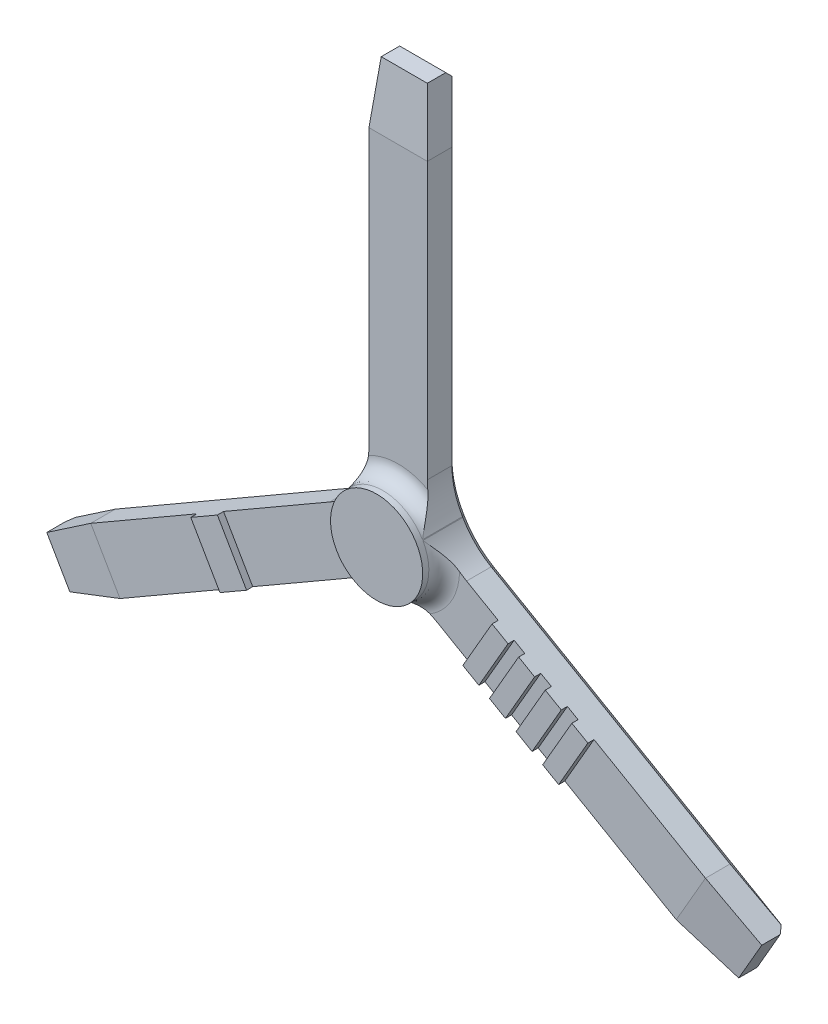
SolidWorks part; units mm, degrees
ref_plane "Front Plane" through (0, 0, 0) normal (0, 0, 1) x (1, 0, 0)
ref_plane "Top Plane" through (0, 0, 0) normal (0, 1, 0) x (1, 0, 0)
ref_plane "Right Plane" through (0, 0, 0) normal (1, 0, 0) x (0, 0, -1)
sketch "Sketch1" plane through (0, 0, 0) normal (0, 0, 1) x (1, 0, 0)
  line L0 (-1.9, 24) -> (1.9, 24) construction
  line L1 (0, 0) -> (0, 24) construction
  line L2 (-1.9, 24) -> (-1.9, 26)
  line L3 (-1.9, 26) -> (1.9, 26)
  line L4 (1.9, 26) -> (1.9, 24)
  line L5 (23.4667, -11.3546) -> (21.5667, -14.6454)
  line L6 (21.5667, -14.6454) -> (19.8346, -13.6454)
  line L7 (21.7346, -10.3546) -> (23.4667, -11.3546)
  line L8 (-21.5667, -14.6454) -> (-23.4667, -11.3546)
  line L9 (-23.4667, -11.3546) -> (-21.7346, -10.3546)
  line L10 (-19.8346, -13.6454) -> (-21.5667, -14.6454)
  line L11 (0, 0) -> (1.9, 24) construction
  line L12 (0, 0) -> (19.8346, -13.6454) construction
  line L13 (-1.9, 24) -> (-1.9, 1.097)
  line L14 (-1.9, 1.097) -> (-21.7346, -10.3546)
  line L15 (-19.8346, -13.6454) -> (0, -2.1939)
  line L16 (0, -2.1939) -> (19.8346, -13.6454)
  line L17 (21.7346, -10.3546) -> (1.9, 1.097)
  line L18 (1.9, 1.097) -> (1.9, 24)
  circle A0 centre (0, 0) radius 24 construction
  dimension "D1" = 48
  dimension "D2" = 3.8
  dimension "D3" = 2
  dimension "D4" = 120
  dimension "D5" = 24.0751
  dimension "D6" = 3
extrude "Boss-Extrude1" add sketch "Sketch1" along normal blind 2 contours L18 A0 L13 L14 L15 L16 L17 region at (0, 0, 0)
chamfer "Chamfer1" distance 4 distance2 0.4 3 edges at (22.5167, -13, 2) (-22.5167, -13, 2) (0, 26, 2) first distance on face at (0, 0, 2)
chamfer "Chamfer2" distance 0.4 distance2 4 3 edges at (23.4667, -11.3546, 0.8) (-1.9, 26, 0.8) (-21.5667, -14.6454, 0.8) first distance on face at (22.5167, -13, 0.8) first distance on face at (0, 26, 0.8) first distance on face at (-22.5167, -13, 0.8)
chamfer "Chamfer3" distance 4 distance2 0.4 3 edges at (1.9, 26, 0.8) (21.5667, -14.6454, 0.8) (-23.4667, -11.3546, 0.8) first distance on face at (1.9, 15.2388, 1.12) first distance on face at (12.2472, -9.2648, 1.12) first distance on face at (-14.1472, -5.9739, 1.12)
sketch "Sketch2" plane through (0, 0, 0) normal (0, 0, -1) x (-1, 0, 0)
  circle A0 centre (0, 0) radius 3
  dimension "D1" = 6
extrude "Boss-Extrude2" add sketch "Sketch2" against normal blind 3.4
fillet "Fillet1" radius 5 6 edges at (1.9, 2.3216, 1) (2.9606, 0.4846, 1) (1.0606, -2.8063, 1) (-1.0606, -2.8063, 1) (-2.9606, 0.4846, 1) (-1.9, 2.3216, 1)
fillet "Fillet2" radius 1 3 edges at (0, 3, 2) (2.5981, -1.5, 2) (-2.5981, -1.5, 2)
chamfer "Chamfer4" distance 0.4 angle 45 18 edges at (22.5167, -13, 0) (-22.5167, -13, 0) (0, 26, 0) (12.2293, -4.8667, 0) (3.4082, 0.4282, 0) (2.5981, 1.5, 0) (2.0749, 2.7374, 0) (1.9, 13.0242, 0) (-12.2293, -4.8667, 0) (-3.4082, 0.4282, 0) (-2.5981, 1.5, 0) (-2.0749, 2.7374, 0) (-1.9, 13.0242, 0) (10.3293, -8.1576, 0) (1.3332, -3.1657, 0) (0, -3, 0) (-1.3332, -3.1657, 0) (-10.3293, -8.1576, 0)
sketch "Sketch3" plane through (0, 0, 2) normal (0, 0, 1) x (1, 0, 0)
  line L0 (-12.2293, -4.8667) -> (-10.3293, -8.1576) construction
  line L1 (-4.4561, -0.3788) -> (-20.0026, -9.3546) construction
  line L2 (-2.5561, -3.6697) -> (-18.1026, -12.6454) construction
  line L3 (-13.0953, -5.3667) -> (-11.1953, -8.6576)
  line L4 (2.5561, -3.6697) -> (18.1026, -12.6454) construction
  line L5 (10.3293, -8.1576) -> (12.2293, -4.8667) construction
  line L6 (20.0026, -9.3546) -> (4.4561, -0.3788) construction
  line L7 (-13.0953, -5.3667) -> (-11.3633, -4.3667)
  line L8 (-11.1953, -8.6576) -> (-9.4633, -7.6576)
  line L9 (-11.3633, -4.3667) -> (-9.4633, -7.6576)
  line L10 (-13.0953, -5.3667) -> (-9.4633, -7.6576) construction
  line L11 (-11.1953, -8.6576) -> (-11.3633, -4.3667) construction
  line L12 (11.7097, -4.5667) -> (9.8097, -7.8576)
  line L13 (11.7097, -4.5667) -> (12.7489, -5.1667)
  line L14 (9.8097, -7.8576) -> (10.8489, -8.4576)
  line L15 (12.7489, -5.1667) -> (10.8489, -8.4576)
  line L16 (11.7097, -4.5667) -> (10.8489, -8.4576) construction
  line L17 (9.8097, -7.8576) -> (12.7489, -5.1667) construction
  line L18 (8.0776, -6.8576) -> (9.1169, -7.4576)
  line L19 (11.0169, -4.1667) -> (9.1169, -7.4576)
  line L20 (9.9776, -3.5667) -> (8.0776, -6.8576)
  line L21 (9.9776, -3.5667) -> (11.0169, -4.1667)
  line L22 (6.3456, -5.8576) -> (7.3848, -6.4576)
  line L23 (9.2848, -3.1667) -> (7.3848, -6.4576)
  line L24 (8.2456, -2.5667) -> (6.3456, -5.8576)
  line L25 (8.2456, -2.5667) -> (9.2848, -3.1667)
  line L26 (4.6135, -4.8576) -> (5.6528, -5.4576)
  line L27 (7.5528, -2.1667) -> (5.6528, -5.4576)
  line L28 (6.5135, -1.5667) -> (4.6135, -4.8576)
  line L29 (6.5135, -1.5667) -> (7.5528, -2.1667)
  point P13 (-11.2793, -6.5121)
  point P14 (11.2793, -6.5121)
  dimension "D1" = 2
  dimension "D2" = 1.2
  dimension "D3" = 4
extrude "Boss-Extrude3" add sketch "Sketch3" along normal blind 0.4
